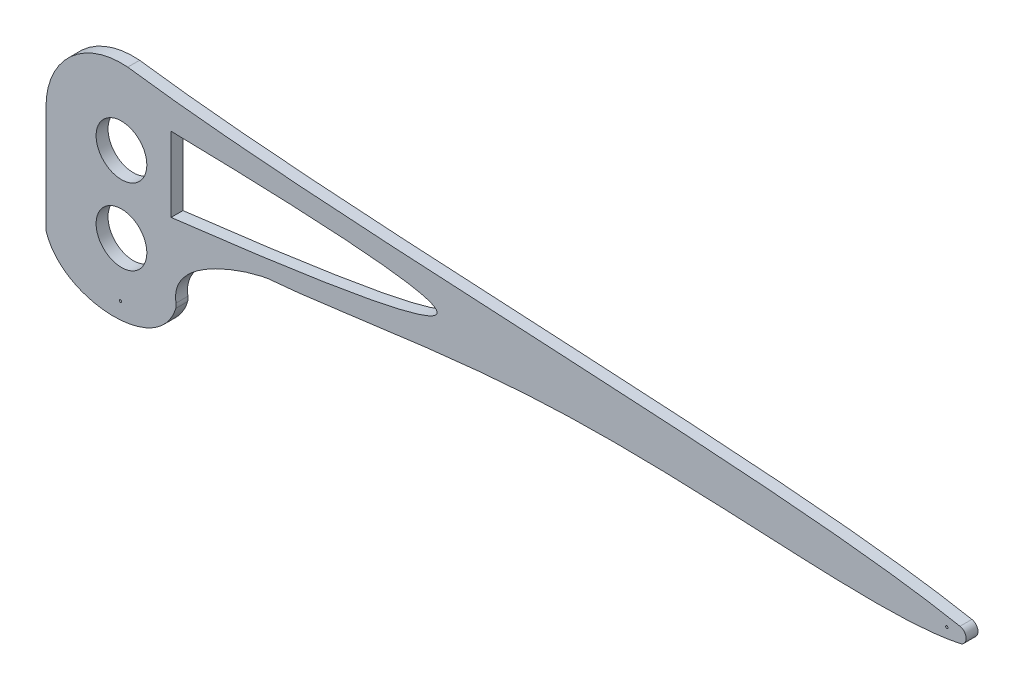
SolidWorks part; units mm, degrees
ref_plane "Front Plane" through (0, 0, 0) normal (0, 0, 1) x (1, 0, 0)
ref_plane "Top Plane" through (0, 0, 0) normal (0, 1, 0) x (1, 0, 0)
ref_plane "Right Plane" through (0, 0, 0) normal (1, 0, 0) x (0, 0, -1)
sketch "Sketch1" plane through (0, 0, 0) normal (0, 0, 1) x (1, 0, 0)
  line L0 (0, 0) -> (0, -25.4) construction
  line L1 (-25.1919, 0) -> (-25.1919, -35.2154)
  arc A1 (279.8894, 2.3729) -> (279.9348, -2.6026) centre (279.4, -0.1195) cw
  arc A2 (2.0902, 25.105) -> (-25.1919, 0) centre (0, 0) ccw
  circle A5 centre (0, -25.4) radius 8.4667
  circle A6 centre (0, 0) radius 8.4667
  arc A8 (18.2122, -35.0564) -> (18.1176, -36.6407) centre (14.8556, -35.6511) cw
  arc A9 (-25.1919, -35.2154) -> (-25.0041, -36.3312) centre (-21.783, -35.2154) ccw
  spline S0 degree 3 poles (2.0902, 25.105) (29.3726, 21.3189) (128.0417, 14.5406) (239.5484, 10.2935) (279.8894, 2.3729) knots 0.008543 0.008543 0.008543 0.008543 0.340595 0.941395 0.941395 0.941395 0.941395
  spline S1 degree 3 poles (50.3146, -12.4878) (67.829, -11.2174) (162.8512, 6.0974) (250.0383, -9.0418) (279.9348, -2.6026) knots 0.235846 0.235846 0.235846 0.235846 0.495201 0.941477 0.941477 0.941477 0.941477
  spline S2 degree 3 poles (18.2122, -35.0564) (15.7223, -21.0033) (45.0837, -12.5774) (50.3146, -12.4878) knots 0.243689 0.243689 0.243689 0.243689 1 1 1 1
  spline S3 degree 3 poles (-25.0041, -36.3312) (-24.3022, -38.3573) (-17.5003, -49.4729) (6.4866, -52.353) (16.8283, -40.8908) (18.1176, -36.6407) knots 0.011286 0.011286 0.011286 0.011286 0.130988 0.750185 0.983992 0.983992 0.983992 0.983992
  point P3 (76.2, 0)
  dimension "D1" = 3.4089
  dimension "D2" = 2.54
  dimension "D3" = 16.9333
  dimension "D6" = 279.4
extrude "Boss-Extrude1" add sketch "Sketch1" along normal blind 3.9688 contours S1 A1 S0 region at (77.9982, -1.3579, 0)
scale "Scale1" scale about centroid uniform scaling yes scale factor 0.75
sketch "Sketch2" plane through (0, 0, 3.4727) normal (0, 0, 1) x (1, 0, 0)
  line L0 (31.9233, -8.6699) -> (31.9233, 10.02)
  spline S1 degree 2 poles (31.9233, 10.02) (165.1103, 7.315) (31.9233, -8.6699) knots 0 0 0 1 1 1
  point P3 (98.5135, 4.0601)
extrude "Cut-Extrude1" cut sketch "Sketch2" against normal through all both and the other way through all
sketch "Sketch3" plane through (0, 0, 3.4727) normal (0, 0, 1) x (1, 0, 0)
  circle A0 centre (19.2662, -33.1495) radius 0.2858
  circle A1 centre (226.1269, -0.3747) radius 0.2857
  dimension "D1" = 0.5715
extrude "Cut-Extrude2" cut sketch "Sketch3" against normal through all both
